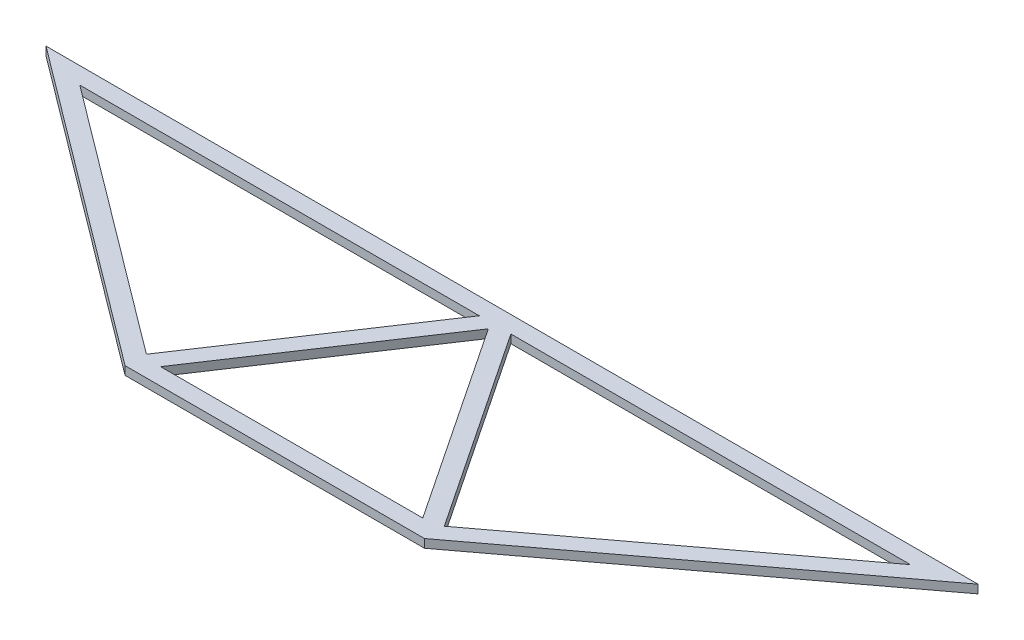
SolidWorks part; units mm, degrees
material "ASTM A500"
ref_plane "Front Plane" through (0, 0, 0) normal (0, 0, 1) x (1, 0, 0)
ref_plane "Top Plane" through (0, 0, 0) normal (0, 1, 0) x (1, 0, 0)
ref_plane "Right Plane" through (0, 0, 0) normal (1, 0, 0) x (0, 0, -1)
sketch "Sketch1" plane through (0, 0, 0) normal (0, 1, 0) x (1, 0, 0)
  line L27 (-434.5, 311.5) -> (-3.8333, -11.5)
  line L28 (-3.8333, -11.5) -> (403.8333, -11.5)
  line L29 (403.8333, -11.5) -> (834.5, 311.5)
  line L30 (834.5, 311.5) -> (-434.5, 311.5)
  line L31 (-365.5, 288.5) -> (-2.8253, 16.494)
  line L32 (21.4879, 11.5) -> (378.5121, 11.5)
  line L33 (402.8253, 16.494) -> (765.5, 288.5)
  line L34 (765.5, 288.5) -> (221.4879, 288.5)
  line L37 (221.4879, 288.5) -> (402.8253, 16.494)
  line L38 (178.5121, 288.5) -> (-2.8253, 16.494)
  line L39 (200, 279.2681) -> (378.5121, 11.5)
  line L40 (200, 279.2681) -> (21.4879, 11.5)
  line L41 (178.5121, 288.5) -> (-365.5, 288.5)
  point P0 (0, 0)
  point P1 (400, 0)
  point P2 (200, 320.7319)
  point P4 (0, 0)
  point P10 (3.8333, 11.5)
  point P11 (396.1667, 11.5)
  point P13 (200, 300)
  point P14 (409.5686, 6.3791)
  point P15 (-9.5686, 6.3791)
  point P17 (390.4314, -6.3791)
  point P18 (9.5686, -6.3791)
extrude "Boss-Extrude2" add sketch "Sketch1" along normal blind 11.5 contours L30 L27 L28 L29
extrude "Cut-Extrude3" cut sketch "Sketch1<8>" along normal up to next contours L39 L40 L32 | L38 L41 L31 | L34 L37 L33 region at (-63.2711, 0, -197.8313) region at (200, 0, -100.756)
sketch "Sketch1<8>" plane through (0, 0, 0) normal (0, 1, 0) x (1, 0, 0) same geometry as "Sketch1"
